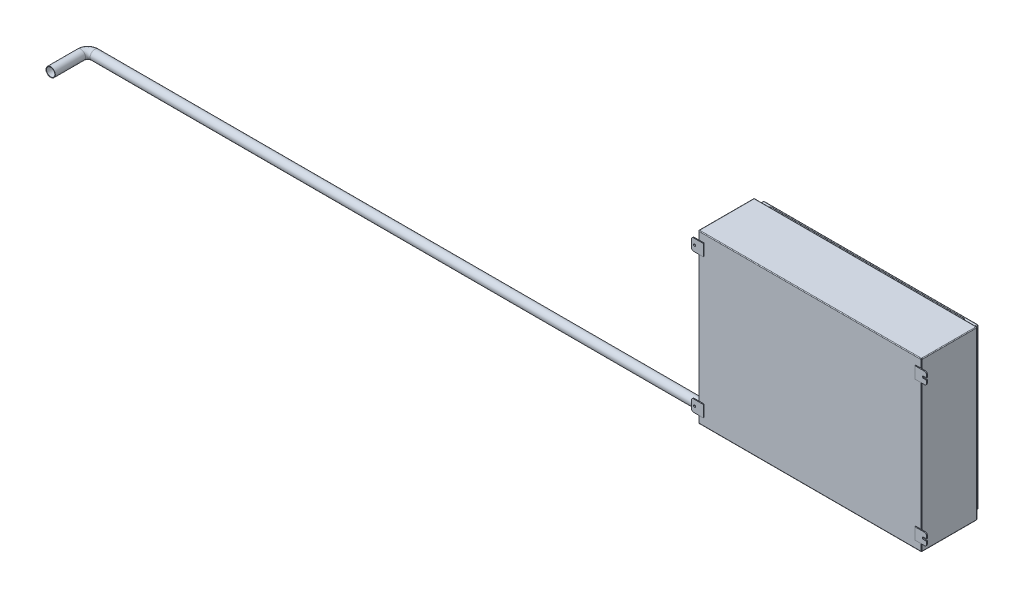
SolidWorks part; units mm, degrees
ref_plane "Front Plane" through (0, 0, 0) normal (0, 0, 1) x (1, 0, 0)
ref_plane "Top Plane" through (0, 0, 0) normal (0, 1, 0) x (1, 0, 0)
ref_plane "Right Plane" through (0, 0, 0) normal (1, 0, 0) x (0, 0, -1)
sketch "Sketch1" plane through (0, 0, 0) normal (0, 0, 1) x (1, 0, 0)
  line L0 (-609.6, -457.2) -> (609.6, 457.2) construction
  line L1 (-609.6, 457.2) -> (609.6, 457.2)
  line L2 (-609.6, 457.2) -> (-609.6, -457.2)
  line L3 (-609.6, -457.2) -> (609.6, -457.2)
  line L4 (609.6, 457.2) -> (609.6, -457.2)
  line L5 (-607.7026, 455.3026) -> (-607.7026, -455.3026)
  line L6 (-607.7026, -455.3026) -> (607.7026, -455.3026)
  line L7 (607.7026, 455.3026) -> (607.7026, -455.3026)
  line L8 (-607.7026, 455.3026) -> (607.7026, 455.3026)
  line L9 (571.5, -419.1) -> (-571.5, 419.1) construction
  line L10 (-571.5, 419.1) -> (571.5, 419.1)
  line L11 (-571.5, 419.1) -> (-571.5, -419.1)
  line L12 (-571.5, -419.1) -> (571.5, -419.1)
  line L13 (571.5, 419.1) -> (571.5, -419.1)
  line L14 (-549.275, 396.875) -> (-549.275, -396.875) construction
  line L15 (-549.275, -396.875) -> (549.275, -396.875) construction
  line L16 (549.275, 396.875) -> (549.275, -396.875) construction
  line L17 (-549.275, 396.875) -> (549.275, 396.875) construction
  line L18 (609.6, 412.75) -> (641.35, 412.75)
  line L19 (641.35, 412.75) -> (641.35, 386.5562)
  line L21 (-641.35, 349.25) -> (-609.6, 349.25)
  line L22 (0, 0) -> (0, 396.875) construction
  line L23 (-609.6, 412.75) -> (-641.35, 412.75)
  line L25 (-641.35, 412.75) -> (-641.35, 349.25)
  line L26 (0, 0) -> (0, 125.3343) construction
  line L27 (-544.5125, 396.875) -> (-544.5125, -396.875) construction
  line L28 (625.475, 375.4437) -> (609.6, 375.4437) construction
  line L29 (-625.475, 381) -> (-625.475, 349.25) construction
  line L30 (641.35, 349.25) -> (609.6, 349.25)
  line L31 (625.475, 375.4437) -> (641.35, 375.4437)
  line L32 (625.475, 386.5562) -> (641.35, 386.5562)
  line L33 (641.35, 375.4437) -> (641.35, 349.25)
  line L34 (625.475, 381) -> (625.475, 412.75) construction
  line L35 (-625.475, 365.125) -> (-609.6, 365.125) construction
  line L36 (0, 0) -> (571.5, 0) construction
  line L37 (-625.475, 381) -> (625.475, 381) construction
  line L38 (-641.35, -349.25) -> (-609.6, -349.25)
  line L39 (-641.35, -412.75) -> (-641.35, -349.25)
  line L40 (-609.6, -412.75) -> (-641.35, -412.75)
  line L41 (641.35, -349.25) -> (609.6, -349.25)
  line L42 (641.35, -375.4437) -> (641.35, -349.25)
  line L43 (625.475, -375.4437) -> (641.35, -375.4437)
  line L44 (641.35, -412.75) -> (641.35, -386.5562)
  line L45 (625.475, -386.5562) -> (641.35, -386.5562)
  line L46 (609.6, -412.75) -> (641.35, -412.75)
  circle A0 centre (549.275, 396.875) radius 4.7625 construction
  circle A1 centre (549.275, -396.875) radius 4.7625 construction
  circle A2 centre (-549.275, -396.875) radius 4.7625 construction
  circle A3 centre (-549.275, 396.875) radius 4.7625 construction
  circle A4 centre (-625.475, 381) radius 5.5563
  arc A6 (625.475, 386.5562) -> (625.475, 375.4437) centre (625.475, 381) ccw
  circle A12 centre (-625.475, -381) radius 5.5563
  arc A13 (625.475, -386.5562) -> (625.475, -375.4437) centre (625.475, -381) cw
  circle A14 centre (0, 396.875) radius 4.7625 construction
  circle A15 centre (0, -396.875) radius 4.7625 construction
  dimension "panel screw hole" = 9.525
  dimension "D6" = 11.1125
  dimension "D1" = 63.5
  dimension "D3" = 1250.95
  dimension "D2" = 22.225
sketch "Sketch2" plane through (0, 0, 0) normal (0, 1, 0) x (1, 0, 0)
  line L0 (-609.6, -152.4) -> (609.6, 152.4) construction
  line L1 (-609.6, 152.4) -> (609.6, 152.4)
  line L2 (-609.6, 152.4) -> (-609.6, -152.4)
  line L3 (-609.6, -152.4) -> (609.6, -152.4)
  line L4 (609.6, 152.4) -> (609.6, -152.4)
  line L5 (-607.7026, 150.5026) -> (-607.7026, -150.5026)
  line L6 (-571.5, -122.8166) -> (571.5, -122.8166)
  line L7 (-571.5, -122.8166) -> (-571.5, -125.4735)
  line L8 (-571.5, -125.4735) -> (571.5, -125.4735)
  line L9 (571.5, -122.8166) -> (571.5, -125.4735)
  line L10 (-607.7026, -150.5026) -> (607.7026, -150.5026)
  line L11 (607.7026, 150.5026) -> (607.7026, -150.5026)
  line L12 (-607.7026, 150.5026) -> (607.7026, 150.5026)
  line L13 (-609.6, 152.4) -> (609.6, 152.4) construction
  line L14 (-574.675, 152.4) -> (-574.675, 150.5026) construction
  line L15 (574.675, 152.4) -> (574.675, 150.5026) construction
  line L16 (-586.613, 173.482) -> (586.613, 173.482) construction
  line L17 (0, 0) -> (0, 173.482) construction
  line L18 (-586.613, 179.9666) -> (586.613, 179.9666) construction
  line L19 (-577.85, -152.4) -> (577.85, -152.4) construction
  line L20 (-641.35, -152.4) -> (-577.85, -152.4)
  line L21 (-641.35, -152.4) -> (-641.35, -157.226)
  line L22 (-641.35, -157.226) -> (-577.85, -157.226)
  line L23 (-577.85, -152.4) -> (-577.85, -157.226)
  line L24 (577.85, -152.4) -> (641.35, -152.4)
  line L25 (577.85, -152.4) -> (577.85, -157.226)
  line L26 (577.85, -157.226) -> (641.35, -157.226)
  line L27 (641.35, -152.4) -> (641.35, -157.226)
  line L28 (0, 0) -> (0, -152.4) construction
  line L29 (-586.613, 181.864) -> (586.613, 181.864) construction
  line L30 (-577.0499, 152.4) -> (-577.0499, 150.5026) construction
  dimension "D4" = 34.925
  dimension "P" = 1173.226
  dimension "D6" = 4.826
  dimension "D2" = 27.686
  dimension "D7" = 1.8974
  dimension "D8" = 29.464
  dimension "D9" = 63.5
  dimension "D10" = 32.5501
  dimension "D3" = 34.925
  dimension "D5" = 21.082
  dimension "D1" = 1.8974
sketch "Sketch4" plane through (0, 0, 0) normal (0, 0, 1) x (1, 0, 0)
  line L1 (-609.6, -457.2) -> (609.6, -457.2) construction
  line L2 (609.6, 457.2) -> (609.6, -457.2) construction
  line L4 (-609.6, 457.2) -> (609.6, 457.2) construction
  line L7 (-609.6, 457.2) -> (-609.6, -457.2) construction
  line L9 (-609.6, -457.2) -> (609.6, -457.2)
  line L10 (609.6, 457.2) -> (609.6, -457.2)
  line L12 (-609.6, 457.2) -> (609.6, 457.2)
  line L15 (-609.6, 457.2) -> (-609.6, -457.2)
extrude "Extrude1" add sketch "Sketch4" along normal mid plane 304.8
sketch "Sketch27" plane through (0, 0, -152.4) normal (0, 0, -1) x (-1, 0, 0)
  line L0 (609.6, 457.2) -> (609.6, -457.2) construction
  line L1 (574.675, -422.275) -> (-574.675, -422.275) construction
  line L2 (574.675, -422.275) -> (574.675, 422.275) construction
  line L3 (574.675, 422.275) -> (-574.675, 422.275) construction
  line L4 (-574.675, -422.275) -> (-574.675, 422.275) construction
  line L5 (609.6, 457.2) -> (-609.6, 457.2) construction
  line L10 (609.6, -457.2) -> (-609.6, -457.2) construction
  line L11 (578.4698, -426.0698) -> (-578.4698, -426.0698)
  line L12 (-578.4698, -426.0698) -> (-578.4698, 426.0698)
  line L13 (578.4698, 426.0698) -> (-578.4698, 426.0698)
  line L14 (578.4698, -426.0698) -> (578.4698, 426.0698)
  dimension "D1" = 34.925
  dimension "D2" = 34.925
  dimension "D3" = 34.925
  dimension "D4" = 3.7948
extrude "Extrude19" add sketch "Sketch27" along normal up to vertex (21.082 mm away) up to point (586.613, 0, -173.482)
fillet "Fillet1" radius 3.7948 20 edges at (609.6, -457.2, 0) (0, -457.2, -152.4) (609.6, 0, -152.4) (609.6, 0, 152.4) (0, -457.2, 152.4) (609.6, 457.2, 0) (0, 457.2, 152.4) (0, 457.2, -152.4) (-609.6, 457.2, 0) (-609.6, 0, 152.4) (-609.6, -457.2, 0) (-609.6, 0, -152.4) (0, 426.0698, -152.4) (578.4698, 0, -152.4) (0, -426.0698, -152.4) (-578.4698, 0, -152.4) (578.4698, -426.0698, -162.941) (578.4698, 426.0698, -162.941) (-578.4698, 426.0698, -162.941) (-578.4698, -426.0698, -162.941)
shell "Shell1" thickness 1.8974
sketch "Sketch5" plane through (0, 0, -173.482) normal (0, 0, -1) x (-1, 0, 0)
  line L8 (-576.5724, 422.275) -> (-576.5724, -422.275)
  line L9 (574.675, 424.1724) -> (-574.675, 424.1724)
  line L10 (576.5724, -422.275) -> (576.5724, 422.275)
  line L11 (-574.675, -424.1724) -> (574.675, -424.1724)
  line L12 (-576.5724, 422.275) -> (-576.5724, -422.275)
  line L13 (574.675, 424.1724) -> (-574.675, 424.1724)
  line L14 (576.5724, -422.275) -> (576.5724, 422.275)
  line L15 (-574.675, -424.1724) -> (574.675, -424.1724)
  arc A4 (-574.675, 424.1724) -> (-576.5724, 422.275) centre (-574.675, 422.275) ccw
  arc A5 (576.5724, 422.275) -> (574.675, 424.1724) centre (574.675, 422.275) ccw
  arc A6 (574.675, -424.1724) -> (576.5724, -422.275) centre (574.675, -422.275) ccw
  arc A7 (-576.5724, -422.275) -> (-574.675, -424.1724) centre (-574.675, -422.275) ccw
  arc A8 (-574.675, 424.1724) -> (-576.5724, 422.275) centre (-574.675, 422.275) ccw
  arc A9 (576.5724, 422.275) -> (574.675, 424.1724) centre (574.675, 422.275) ccw
  arc A10 (574.675, -424.1724) -> (576.5724, -422.275) centre (574.675, -422.275) ccw
  arc A11 (-576.5724, -422.275) -> (-574.675, -424.1724) centre (-574.675, -422.275) ccw
  dimension "D1" = 0
extrude "Cut-Extrude1" cut sketch "Sketch5" against normal blind 1.8974
sketch "Sketch50" plane through (0, 0, -152.4) normal (0, 0, -1) x (-1, 0, 0)
  line L0 (-609.6, 0) -> (-582.2645, 0) construction
  line L1 (-582.2645, -422.275) -> (-582.2645, 422.275) construction
  line L2 (-609.6, -453.4052) -> (-609.6, 453.4052) construction
  dimension "D1" = 27.3355
sketch "Sketch6" plane through (0, 0, 152.4) normal (0, 0, 1) x (1, 0, 0)
  line L6 (-641.35, 349.25) -> (-609.6, 349.25) construction
  line L7 (-609.6, 412.75) -> (-641.35, 412.75) construction
  line L8 (-641.35, 412.75) -> (-641.35, 349.25) construction
  line L9 (-641.35, 349.25) -> (-609.6, 349.25)
  line L10 (-609.6, 412.75) -> (-641.35, 412.75)
  line L11 (-641.35, 412.75) -> (-641.35, 349.25)
  line L12 (641.35, 349.25) -> (609.6, 349.25) construction
  line L13 (641.35, 375.4437) -> (641.35, 349.25) construction
  line L14 (625.475, 375.4437) -> (641.35, 375.4437) construction
  line L15 (625.475, 386.5562) -> (641.35, 386.5562) construction
  line L16 (641.35, 412.75) -> (641.35, 386.5562) construction
  line L17 (609.6, 412.75) -> (641.35, 412.75) construction
  line L18 (641.35, 349.25) -> (609.6, 349.25)
  line L19 (641.35, 375.4437) -> (641.35, 349.25)
  line L20 (625.475, 375.4437) -> (641.35, 375.4437)
  line L21 (625.475, 386.5562) -> (641.35, 386.5562)
  line L22 (641.35, 412.75) -> (641.35, 386.5562)
  line L23 (609.6, 412.75) -> (641.35, 412.75)
  line L24 (-609.6, 412.75) -> (-577.85, 412.75)
  line L25 (-577.85, 412.75) -> (-577.85, 349.25)
  line L26 (-609.6, 349.25) -> (-577.85, 349.25)
  line L27 (609.6, 412.75) -> (577.85, 412.75)
  line L28 (577.85, 412.75) -> (577.85, 349.25)
  line L29 (609.6, 349.25) -> (577.85, 349.25)
  line L30 (0, 0) -> (609.6, 0) construction
  line L31 (609.6, 457.2) -> (609.6, -457.2) construction
  line L32 (609.6, -349.25) -> (577.85, -349.25)
  line L33 (577.85, -412.75) -> (577.85, -349.25)
  line L34 (609.6, -412.75) -> (577.85, -412.75)
  line L35 (-609.6, -349.25) -> (-577.85, -349.25)
  line L36 (-577.85, -412.75) -> (-577.85, -349.25)
  line L37 (-609.6, -412.75) -> (-577.85, -412.75)
  line L38 (609.6, -412.75) -> (641.35, -412.75)
  line L39 (641.35, -412.75) -> (641.35, -386.5562)
  line L40 (625.475, -386.5562) -> (641.35, -386.5562)
  line L41 (625.475, -375.4437) -> (641.35, -375.4437)
  line L42 (641.35, -375.4437) -> (641.35, -349.25)
  line L43 (641.35, -349.25) -> (609.6, -349.25)
  line L44 (-641.35, -412.75) -> (-641.35, -349.25)
  line L45 (-609.6, -412.75) -> (-641.35, -412.75)
  line L46 (-641.35, -349.25) -> (-609.6, -349.25)
  circle A7 centre (-625.475, 381) radius 5.5563 construction
  circle A8 centre (-625.475, 381) radius 5.5563
  arc A9 (625.475, 386.5562) -> (625.475, 375.4437) centre (625.475, 381) ccw construction
  arc A10 (625.475, 386.5562) -> (625.475, 375.4437) centre (625.475, 381) ccw
  arc A11 (625.475, -386.5562) -> (625.475, -375.4437) centre (625.475, -381) cw
  circle A12 centre (-625.475, -381) radius 5.5563
extrude "Extrude2" add sketch "Sketch6" along normal up to vertex (4.826 mm away) up to point (641.35, 0, 157.226)
sketch "Sketch16" plane through (0, 0, 150.5026) normal (0, 0, -1) x (-1, 0, 0)
  circle A0 centre (-549.275, 396.875) radius 8.3344
  circle A1 centre (549.275, 396.875) radius 8.3344
  circle A2 centre (549.275, -396.875) radius 8.3344
  circle A3 centre (-549.275, -396.875) radius 8.3344
  circle A4 centre (-549.275, 396.875) radius 4.7625 construction
  circle A5 centre (-549.275, -396.875) radius 4.7625 construction
  circle A6 centre (549.275, -396.875) radius 4.7625 construction
  circle A7 centre (0, 396.875) radius 8.3344
  circle A8 centre (-549.275, 396.875) radius 4.7625
  circle A9 centre (-549.275, -396.875) radius 4.7625
  circle A10 centre (549.275, -396.875) radius 4.7625
  circle A13 centre (549.275, 396.875) radius 4.7625
  circle A16 centre (0, 396.875) radius 4.7625 construction
  circle A17 centre (0, 396.875) radius 4.7625
  circle A18 centre (0, -396.875) radius 8.3344
  circle A19 centre (0, -396.875) radius 4.7625 construction
  circle A20 centre (0, -396.875) radius 4.7625
  dimension "D1" = 16.6688
  dimension "D2" = 9.525
extrude "Extrude6" add sketch "Sketch16" along normal up to vertex (25.0292 mm away) up to point (571.5, 0, 125.4735)
sketch "Sketch17" plane through (0, 0, 150.5026) normal (0, 0, -1) x (-1, 0, 0)
  circle A1 centre (-549.275, 396.875) radius 4.7625
  circle A2 centre (-549.275, 396.875) radius 4.7625
  circle A5 centre (0, -396.875) radius 4.7625 construction
  circle A6 centre (0, -396.875) radius 4.7625
  circle A11 centre (549.275, 396.875) radius 4.7625
  circle A12 centre (549.275, 396.875) radius 4.7625
  circle A13 centre (549.275, -396.875) radius 4.7625
  circle A14 centre (549.275, -396.875) radius 4.7625
  circle A15 centre (-549.275, -396.875) radius 4.7625
  circle A16 centre (-549.275, -396.875) radius 4.7625
  circle A20 centre (0, 396.875) radius 4.7625 construction
  circle A21 centre (0, 396.875) radius 4.7625
  dimension "D1" = 0
  dimension "D6" = 0
  dimension "D7" = 0
  dimension "D8" = 0
extrude "Extrude7" add sketch "Sketch17" along normal offset from surface (40.9042 mm away) 15.875 up to face at (540.9406, 396.875, 125.4735) offset beyond the face yes
sketch "Sketch18" plane through (0, 0, 125.4735) normal (0, 0, -1) x (-1, 0, 0)
  line L0 (571.5, -419.1) -> (-571.5, -419.1) construction
  line L1 (571.5, 419.1) -> (571.5, -419.1) construction
  line L2 (571.5, 419.1) -> (-571.5, 419.1) construction
  line L3 (-571.5, 419.1) -> (-571.5, -419.1) construction
  line L4 (571.5, -419.1) -> (-571.5, -419.1)
  line L5 (571.5, 419.1) -> (571.5, -419.1)
  line L6 (571.5, 419.1) -> (-571.5, 419.1)
  line L7 (-571.5, 419.1) -> (-571.5, -419.1)
  circle A1 centre (549.275, 396.875) radius 5.5245
  circle A2 centre (549.275, -396.875) radius 5.5245
  circle A3 centre (549.275, -396.875) radius 5.5245
  circle A4 centre (-549.275, 396.875) radius 5.5245
  circle A5 centre (-549.275, -396.875) radius 5.5245
  dimension "D1" = 0.762
extrude "Extrude8" add sketch "Sketch18" along normal up to vertex (2.6568 mm away) up to point (571.5, 0, 122.8166)
ref_plane "Plane1" through (0, 0, -181.864) normal (0, 0, 1) x (1, 0, 0)
sketch "Sketch7" plane through (0, 0, -181.864) normal (0, 0, 1) x (1, 0, 0)
  line L0 (-609.6, 457.2) -> (609.6, 457.2) construction
  line L1 (-586.613, 441.198) -> (586.613, 441.198)
  line L2 (-586.613, 441.198) -> (-586.613, -431.8)
  line L3 (-586.613, -431.8) -> (586.613, -431.8)
  line L4 (586.613, 441.198) -> (586.613, -431.8)
  line L5 (-609.6, -457.2) -> (609.6, -457.2) construction
  line L6 (0, 0) -> (0, -431.8) construction
  line L7 (-609.6, -457.2) -> (609.6, 457.2) construction
  dimension "D1" = 872.998
  dimension "D2" = 25.4
  dimension "D3" = 16.002
  dimension "D4" = 1173.226
extrude "Extrude3" add sketch "Sketch7" along normal blind 17.4625 separate body
fillet "Fillet2" radius 3.7948 8 edges at (0, -431.8, -181.864) (586.613, 4.699, -181.864) (0, 441.198, -181.864) (-586.613, 4.699, -181.864) (-586.613, -431.8, -173.1327) (-586.613, 441.198, -173.1327) (586.613, -431.8, -173.1327) (586.613, 441.198, -173.1327)
shell "Shell2" thickness 1.8974 removed face at (0, 4.699, -164.4015)
ref_plane "Plane2" through (0, 437.4032, 0) normal (0, 1, 0) x (-1, 0, 0)
sketch "Sketch8" plane through (0, 437.4032, 0) normal (0, 1, 0) x (-1, 0, 0)
  line L0 (-586.613, -164.4015) -> (-584.7156, -164.4015)
  line L1 (-584.7156, -164.4015) -> (-584.7156, -163.3753)
  line L2 (-588.0177, -160.9663) -> (-593.0976, -162.5947)
  line L3 (-593.0976, -162.5947) -> (-592.5184, -164.4015)
  line L4 (-592.5184, -164.4015) -> (-587.4385, -162.7731)
  line L5 (-586.613, -164.4015) -> (-586.613, -163.3753)
  line L7 (-586.613, -164.4015) -> (-586.613, -178.0692) construction
  line L8 (582.8182, -164.4015) -> (-582.8182, -164.4015) construction
  line L10 (-190.1607, -160.8455) -> (-179.6224, -160.8455) construction
  arc A0 (-584.7156, -163.3753) -> (-588.0177, -160.9663) centre (-587.2455, -163.3753) ccw
  arc A1 (-587.4385, -162.7731) -> (-586.613, -163.3753) centre (-587.2455, -163.3753) cw
  dimension "D5" = 0.6325
  dimension "D4" = 1.8974
  dimension "D2" = 8.382
  dimension "D3" = 3.556
sketch "Sketch9" plane through (0, 0, -164.4015) normal (0, 0, 1) x (1, 0, 0)
  line L0 (586.613, -428.0052) -> (586.613, 437.4032) construction
  line L1 (-582.8182, -431.8) -> (582.8182, -431.8) construction
  line L2 (586.613, -428.0052) -> (586.613, 437.4032)
  line L3 (-582.8182, -431.8) -> (582.8182, -431.8)
  line L4 (-586.613, 437.4032) -> (-586.613, -428.0052) construction
  line L5 (-586.613, 437.4032) -> (-586.613, -428.0052)
  arc A0 (582.8182, -431.8) -> (586.613, -428.0052) centre (582.8182, -428.0052) ccw construction
  arc A1 (582.8182, -431.8) -> (586.613, -428.0052) centre (582.8182, -428.0052) ccw
  arc A2 (-586.613, -428.0052) -> (-582.8182, -431.8) centre (-582.8182, -428.0052) ccw construction
  arc A3 (-586.613, -428.0052) -> (-582.8182, -431.8) centre (-582.8182, -428.0052) ccw
sweep "Sweep1" add profiles "Sketch8" path "Sketch9"
sketch "Sketch10" plane through (0, 0, -164.4015) normal (0, 0, 1) x (1, 0, 0)
  line L1 (-654.9517, 519.8491) -> (654.9517, 519.8491)
  line L2 (-654.9517, 519.8491) -> (-654.9517, 392.8491)
  line L3 (-654.9517, 392.8491) -> (654.9517, 392.8491)
  line L4 (654.9517, 519.8491) -> (654.9517, 392.8491)
  line L5 (-654.9517, -392.8491) -> (-527.9517, -392.8491)
  line L6 (-654.9517, -392.8491) -> (-654.9517, -519.8491)
  line L7 (-654.9517, -519.8491) -> (-527.9517, -519.8491)
  line L8 (-527.9517, -392.8491) -> (-527.9517, -519.8491)
  line L9 (527.9517, -392.8491) -> (654.9517, -392.8491)
  line L10 (527.9517, -392.8491) -> (527.9517, -519.8491)
  line L11 (527.9517, -519.8491) -> (654.9517, -519.8491)
  line L12 (654.9517, -392.8491) -> (654.9517, -519.8491)
  line L14 (-591.4517, -392.8491) -> (-591.4517, 392.8491) construction
  line L17 (-591.4517, 0) -> (0, 0) construction
  line L18 (-527.9517, -456.3491) -> (527.9517, -456.3491) construction
  line L19 (0, -456.3491) -> (0, 0) construction
  dimension "D5" = 127
  dimension "D1" = 785.6982
  dimension "D2" = 1055.9034
extrude "Cut-Extrude2" cut sketch "Sketch10" along normal blind 12.7 draft 30 draft outward yes
sketch "Sketch11" plane through (0, 0, -181.864) normal (0, 0, -1) x (-1, 0, 0)
  line L0 (527.0115, -432.6255) -> (528.0589, -438.2846)
  line L1 (528.0589, -438.2846) -> (523.7442, -438.2846)
  line L2 (527.0115, -432.6255) -> (523.7442, -438.2846)
  line L3 (527.0115, -432.6255) -> (527.9517, -437.7054) construction
  line L4 (-526.9085, -438.2846) -> (526.9085, -438.2846) construction
  line L5 (587.4385, -391.9089) -> (593.0976, -392.9563)
  line L6 (593.0976, -392.9563) -> (593.0976, -388.6416)
  line L7 (593.0976, -388.6416) -> (587.4385, -391.9089)
  line L8 (592.5184, -392.8491) -> (587.4385, -391.9089) construction
  line L9 (593.0976, -391.8059) -> (593.0976, 391.8059) construction
  line L10 (592.5184, 0) -> (16.547, 0) construction
  line L11 (592.5184, -392.8491) -> (592.5184, 392.8491) construction
  line L12 (593.0976, 388.6416) -> (587.4385, 391.9089)
  line L13 (593.0976, 392.9563) -> (593.0976, 388.6416)
  line L14 (587.4385, 391.9089) -> (593.0976, 392.9563)
  line L15 (0, -437.7054) -> (0, -6.7093) construction
  line L16 (-527.9517, -437.7054) -> (527.9517, -437.7054) construction
  line L17 (-587.4385, 391.9089) -> (-593.0976, 392.9563)
  line L18 (-593.0976, 392.9563) -> (-593.0976, 388.6416)
  line L19 (-593.0976, 388.6416) -> (-587.4385, 391.9089)
  line L20 (-593.0976, -388.6416) -> (-587.4385, -391.9089)
  line L21 (-593.0976, -392.9563) -> (-593.0976, -388.6416)
  line L22 (-587.4385, -391.9089) -> (-593.0976, -392.9563)
  line L23 (-527.0115, -432.6255) -> (-523.7442, -438.2846)
  line L24 (-528.0589, -438.2846) -> (-523.7442, -438.2846)
  line L25 (-527.0115, -432.6255) -> (-528.0589, -438.2846)
  ellipse E0 centre (527.3592, -432.4325) end of major axis (527.3592, -433.0649) minor radius 0.3652 (527.3592, -431.8) -> (527.0115, -432.6255) ccw construction
  ellipse E1 centre (587.2455, -392.2566) end of major axis (587.8779, -392.2566) minor radius 0.3652 (587.4385, -391.9089) -> (586.613, -392.2566) ccw construction
  dimension "D1" = 60
  dimension "D2" = 60
extrude "Cut-Extrude3" cut sketch "Sketch11" against normal through all
sketch "Sketch12" plane through (0, 0, 0) normal (1, 0, 0) x (0, 0, -1)
  line L1 (163.4528, 447.8788) -> (163.4528, 439.3006) construction
  line L2 (163.4528, 439.3006) -> (178.0692, 439.3006) construction
  line L3 (178.0692, 439.3006) -> (178.0692, 437.4032) construction
  line L4 (178.0692, 437.4032) -> (161.5554, 437.4032) construction
  line L5 (161.5554, 437.4032) -> (161.5554, 443.7109) construction
  line L7 (178.0692, 439.3006) -> (164.4015, 439.3006) construction
  line L8 (152.4, 447.8788) -> (152.4, 429.8645)
  line L9 (152.4, 429.8645) -> (154.2974, 429.8645)
  line L10 (154.2974, 429.8645) -> (154.2974, 443.7109)
  line L11 (154.2974, 443.7109) -> (157.9264, 447.8788) construction
  line L12 (154.2974, 443.7109) -> (154.2974, 447.8788)
  line L13 (155.9499, 444.8353) -> (154.6959, 443.395)
  line L16 (178.0692, 437.4032) -> (178.0692, -428.0052) construction
  line L17 (148.6052, 453.4052) -> (-148.6052, 453.4052) construction
  line L18 (164.4015, 441.198) -> (164.4015, 437.4032) construction
  line L19 (152.4, 453.4052) -> (152.4, -453.4052) construction
  arc A4 (155.9499, 444.8353) -> (154.2974, 447.8788) centre (157.9264, 447.8788) ccw
  arc A5 (154.6959, 443.395) -> (152.4, 447.8788) centre (157.9264, 447.8788) ccw
  dimension "D1" = 1.8974
  dimension "D4" = 1.8974
  dimension "D3" = 0.508
  dimension "D2" = 0.9487
extrude "Extrude4" add sketch "Sketch12" along normal mid plane 1055.9034 separate body
sketch "Sketch13" plane through (0, 0, 0) normal (1, 0, 0) x (0, 0, -1)
  line L0 (179.9666, 439.3006) -> (163.4528, 439.3006)
  line L1 (163.4528, 447.8788) -> (163.4528, 439.3006) construction
  line L2 (161.5554, 437.4032) -> (161.5554, 443.7109) construction
  line L3 (179.9666, 439.3006) -> (179.9666, 437.4032)
  line L4 (179.9666, 437.4032) -> (161.5554, 437.4032)
  line L5 (163.4528, 447.8788) -> (163.4528, 439.3006)
  line L6 (161.5554, 437.4032) -> (161.5554, 443.7109)
  line L10 (178.0692, 439.3006) -> (164.4015, 439.3006) construction
  line L13 (179.9666, -428.0052) -> (179.9666, 437.4032) construction
  line L14 (152.4, 429.8645) -> (154.2974, 429.8645) construction
  arc A0 (163.4528, 447.8788) -> (161.5554, 443.7109) centre (157.9264, 447.8788) ccw
  arc A1 (154.6959, 443.395) -> (152.4, 447.8788) centre (157.9264, 447.8788) ccw construction
  circle A2 centre (157.9264, 447.8788) radius 3.629
  arc A4 (155.9499, 444.8353) -> (154.2974, 447.8788) centre (157.9264, 447.8788) ccw construction
extrude "Extrude5" add sketch "Sketch13" along normal mid plane 1055.9034 separate body
sketch "Sketch14" plane through (0, 306.3189, -152.4) normal (0, 0, 1) x (1, 0, 0)
  line L1 (-21.1181, 147.0863) -> (21.1181, 147.0863)
  line L2 (-21.1181, 147.0863) -> (-21.1181, 134.7635)
  line L3 (-21.1181, 134.7635) -> (21.1181, 134.7635)
  line L4 (21.1181, 147.0863) -> (21.1181, 134.7635)
  line L5 (527.9517, 147.0863) -> (-527.9517, 147.0863) construction
  line L7 (527.9517, 123.5456) -> (-527.9517, 123.5456) construction
  line L8 (0, -306.3189) -> (0, 134.7635) construction
  line L9 (-527.9517, 136.0335) -> (527.9517, 136.0335) construction
  dimension "D1" = 1055.9034
  dimension "D2" = 42.2361
  dimension "D3" = 1.27
extrude "Cut-Extrude4" cut sketch "Sketch14" against normal mid plane 25.4
pattern_linear "LPattern1" count 8 spacing 84.4723 along (-1, 0, 0) count 8 spacing 84.4723 along (1, 0, 0) of "Cut-Extrude4"
sketch "Sketch15" plane through (0, 216.0613, -161.5554) normal (0, 0, 1) x (1, 0, 0)
  line L0 (-21.1181, 225.0211) -> (21.1181, 225.0211) construction
  line L1 (-63.3542, 225.9101) -> (-21.1181, 225.9101)
  line L2 (-63.3542, 225.9101) -> (-63.3542, 237.3439)
  line L3 (-63.3542, 237.3439) -> (-21.1181, 237.3439)
  line L4 (-21.1181, 225.9101) -> (-21.1181, 237.3439)
  line L7 (527.9517, 237.3439) -> (-527.9517, 237.3439) construction
  line L8 (-527.9517, 226.2911) -> (527.9517, 226.2911) construction
  dimension "D1" = 0.381
extrude "Cut-Extrude5" cut sketch "Sketch15" along normal through all and the other way through all
pattern_linear "LPattern2" count 8 spacing 84.4723 along (-1, 0, 0) count 8 spacing 84.4723 along (1, 0, 0) of "Cut-Extrude5"
combine bodies "Combine1" operation type add bodies to combine 113 107
combine bodies "Combine2" operation type add bodies to combine 118 111
sketch "Sketch28" plane through (527.9517, 0, 0) normal (1, 0, 0) x (0, 0, -1)
  circle A0 centre (157.9264, 447.8788) radius 3.629
  circle A1 centre (157.9264, 447.8788) radius 3.629 construction
extrude "Extrude20" add sketch "Sketch28" against normal up to surface (1055.9034 mm away) separate body up to face at (-527.9517, 447.8788, -161.5554)
ref_plane "Plane3" through (571.5, 0, 0) normal (1, 0, 0) x (0, 0, -1)
ref_plane "Plane5" through (-0.254, 0, 0) normal (1, 0, 0) x (0, 0, -1)
sketch "Sketch29" plane through (-0.254, 0, 0) normal (1, 0, 0) x (0, 0, -1)
  line L0 (178.0692, -431.8) -> (164.2745, -431.8)
  line L1 (164.2745, -431.8) -> (164.2745, -453.4052)
  line L2 (178.0692, -431.8) -> (178.0692, -433.6974)
  line L3 (178.0692, -433.6974) -> (166.1719, -433.6974)
  line L4 (166.1719, -433.6974) -> (166.1719, -453.4052)
  line L5 (164.2745, -453.4052) -> (166.1719, -453.4052)
  line L6 (178.0692, -431.8) -> (164.4015, -431.8) construction
  line L7 (152.4, -453.4052) -> (148.6052, -453.4052) construction
  dimension "D1" = 1.8974
  dimension "D2" = 0.127
extrude "Extrude21" add sketch "Sketch29" along normal mid plane 53.975 separate body
fillet "Fillet6" radius 6.35 4 edges at (26.7335, -432.7487, -178.0692) (-27.2415, -432.7487, -178.0692) (-27.2415, -453.4052, -165.2232) (26.7335, -453.4052, -165.2232)
fillet "Fillet7" radius 2.032 1 edges at (-0.254, -431.8, -164.2745)
fillet "Fillet8" radius 0.254 1 edges at (-0.254, -433.6974, -166.1719)
sketch "Sketch30" plane through (0, 0, -166.1719) normal (0, 0, -1) x (-1, 0, 0)
  line L0 (0.254, -453.4052) -> (0.254, -450.2302) construction
  line L1 (12.554, -443.0801) -> (-12.0459, -443.0801)
  line L2 (-20.3835, -453.4052) -> (20.8915, -453.4052) construction
  line L3 (12.554, -450.2302) -> (-12.0459, -450.2302)
  arc A0 (12.554, -443.0801) -> (12.554, -450.2302) centre (12.554, -446.6552) cw
  arc A1 (-12.0459, -443.0801) -> (-12.0459, -450.2302) centre (-12.0459, -446.6552) ccw
  dimension "D1" = 31.75
  dimension "D2" = 7.1501
  dimension "D3" = 3.175
extrude "Cut-Extrude6" cut sketch "Sketch30" against normal up to vertex (1.8974 mm away) up to point (26.7335, -433.832, -164.2745)
ref_plane "Plane6" through (0, -446.6552, 0) normal (0, 1, 0) x (-1, 0, 0)
sketch "Sketch31" plane through (0, -446.6552, 0) normal (0, 1, 0) x (-1, 0, 0)
  line L0 (0.254, -164.2745) -> (0.254, -175.0619) construction
  line L1 (-6.096, -184.5869) -> (6.604, -184.5869)
  line L2 (-12.446, -178.2369) -> (-12.446, -152.4)
  line L3 (-12.446, -152.4) -> (12.954, -152.4)
  line L4 (12.954, -178.2369) -> (12.954, -152.4)
  line L5 (-605.8052, -152.4) -> (605.8052, -152.4) construction
  line L6 (-20.3835, -164.2745) -> (20.8915, -164.2745) construction
  line L8 (0.254, -181.4119) -> (0.254, -184.5869) construction
  circle A0 centre (0.254, -175.0619) radius 6.35
  arc A1 (6.604, -184.5869) -> (12.954, -178.2369) centre (6.604, -178.2369) ccw
  arc A2 (-6.096, -184.5869) -> (-12.446, -178.2369) centre (-6.096, -178.2369) cw
  point P15 (12.954, -184.5869)
  point P19 (-12.446, -184.5869)
  dimension "D3" = 12.7
  dimension "D4" = 2.54
  dimension "D5" = 6.35
  dimension "D1" = 25.4
  dimension "D2" = 3.175
extrude "Extrude22" add sketch "Sketch31" along normal mid plane 2.032 separate body
sketch "Sketch32" plane through (0, -447.6712, 0) normal (0, -1, 0) x (1, 0, 0)
  line L0 (-12.954, -178.2369) -> (-12.954, -152.4) construction
  line L1 (12.446, -152.4) -> (-12.954, -152.4)
  line L2 (12.446, -152.4) -> (12.446, -154.432)
  line L3 (12.446, -154.432) -> (-12.954, -154.432)
  line L4 (-12.954, -152.4) -> (-12.954, -154.432)
  dimension "D1" = 2.032
extrude "Extrude23" add sketch "Sketch32" against normal blind 15.875
fillet "Fillet11" radius 9.525 8 edges at (641.35, -349.25, 154.813) (641.35, 349.25, 154.813) (641.35, 412.75, 154.813) (641.35, -412.75, 154.813) (-641.35, -412.75, 154.813) (-641.35, -349.25, 154.813) (-641.35, 412.75, 154.813) (-641.35, 349.25, 154.813)
combine bodies "Combine6" operation type add bodies to combine 162 114
sketch "Sketch33" plane through (0, 0, -152.4) normal (0, 0, -1) x (-1, 0, 0)
  line L1 (13.6677, 28.575) -> (-13.6677, 28.575)
  line L2 (13.6677, 28.575) -> (13.6677, 15.875)
  line L3 (13.6677, -28.575) -> (-13.6677, -28.575)
  line L4 (-13.6677, 28.575) -> (-13.6677, -28.575)
  line L6 (13.6677, 15.875) -> (-0.9677, 15.875)
  line L7 (-0.9677, 15.875) -> (-0.9677, -15.875)
  line L8 (-0.9677, -15.875) -> (13.6677, -15.875)
  line L9 (13.6677, -15.875) -> (13.6677, -28.575)
  line L10 (-13.6677, 0) -> (-0.9677, 0) construction
  line L11 (0, -28.575) -> (0, 0) construction
  dimension "D1" = 57.15
  dimension "D2" = 12.7
  dimension "D3" = 27.3355
extrude "Extrude24" [suppressed] add sketch "Sketch33" along normal blind 2.032 separate body
sketch "Sketch34" [suppressed] plane through (0, 0, -154.432) normal (0, 0, -1) x (-1, 0, 0)
  line L1 (-13.6677, 10.4775) -> (-0.9677, 10.4775)
  line L2 (-13.6677, 10.4775) -> (-13.6677, -10.4775)
  line L3 (-13.6677, -10.4775) -> (-0.9677, -10.4775)
  line L4 (-0.9677, 10.4775) -> (-0.9677, -10.4775)
  line L5 (-0.9677, -15.875) -> (-0.9677, 15.875) construction
  line L6 (-13.6677, 0) -> (-0.9677, 0) construction
  line L7 (-13.6677, 28.575) -> (-13.6677, -28.575) construction
  dimension "D1" = 20.955
extrude "Extrude25" [suppressed] add sketch "Sketch34" along normal blind 12.065
sketch "Sketch35" [suppressed] plane through (13.6677, 0, 0) normal (1, 0, 0) x (0, 0, -1)
  line L0 (166.497, 10.4775) -> (154.432, 10.4775) construction
  line L1 (152.4, 7.3025) -> (163.322, 7.3025)
  line L2 (152.4, 7.3025) -> (152.4, -7.3025)
  line L3 (152.4, -7.3025) -> (163.322, -7.3025)
  line L4 (163.322, 7.3025) -> (163.322, -7.3025)
  line L5 (166.497, 10.4775) -> (166.497, -10.4775) construction
  line L6 (166.497, -10.4775) -> (154.432, -10.4775) construction
  line L7 (152.4, 28.575) -> (152.4, -28.575) construction
  dimension "D1" = 3.175
  dimension "D2" = 3.175
  dimension "D3" = 3.175
extrude "Cut-Extrude7" [suppressed] cut sketch "Sketch35" against normal through all
fillet "Fillet9" [suppressed] radius 2.032
fillet "Fillet10" [suppressed] radius 4.064
sketch "Sketch36" [suppressed] plane through (0, 0, -166.497) normal (0, 0, -1) x (-1, 0, 0)
  line L0 (-13.6677, -6.4135) -> (-0.9677, 6.4135) construction
  circle A0 centre (-7.3177, 0) radius 3.175
  dimension "D1" = 6.35
extrude "Cut-Extrude8" [suppressed] cut sketch "Sketch36" against normal through all
ref_plane "Plane7" [suppressed] through (0, 0, 0) normal (0, 1, 0) x (-1, 0, 0)
sketch "Sketch37" [suppressed] plane through (0, 0, 0) normal (0, 1, 0) x (-1, 0, 0)
  line L0 (6.176, -162.5041) -> (6.176, -173.6166)
  line L1 (1.4135, -178.3791) -> (-16.049, -178.3791)
  line L2 (-20.8115, -173.6166) -> (-20.8115, -160.2816)
  line L3 (-16.049, -155.5191) -> (-7.3177, -155.5191)
  line L4 (-7.3177, -166.497) -> (-7.3177, -178.3791) construction
  line L5 (-10.4927, -166.497) -> (-4.1427, -166.497) construction
  arc A0 (6.176, -173.6166) -> (1.4135, -178.3791) centre (1.4135, -173.6166) cw
  arc A1 (-16.049, -178.3791) -> (-20.8115, -173.6166) centre (-16.049, -173.6166) cw
  arc A2 (-20.8115, -160.2816) -> (-16.049, -155.5191) centre (-16.049, -160.2816) cw
  point P11 (6.176, -178.3791)
  point P14 (-20.8115, -178.3791)
  dimension "D3" = 4.7625
  dimension "D4" = 15.875
  dimension "D1" = 26.9875
  dimension "D2" = 22.86
  dimension "D5" = 11.8821
extrude "Extrude-Thin1" [suppressed] add sketch "Sketch37" along normal mid plane 31.75 separate body thin thin type one direction wall 2.54
sketch "Sketch38" [suppressed] plane through (0, 0, -155.5191) normal (0, 0, 1) x (1, 0, 0)
  line L0 (13.6677, 5.2705) -> (0.9677, 5.2705) construction
  line L1 (7.3177, 15.875) -> (20.8115, 15.875)
  line L2 (7.3177, 15.875) -> (7.3177, 5.2705)
  line L3 (7.3177, 5.2705) -> (20.8115, 5.2705)
  line L4 (20.8115, 15.875) -> (20.8115, 5.2705)
  line L5 (7.3177, -5.2705) -> (20.8115, -5.2705)
  line L6 (7.3177, -5.2705) -> (7.3177, -15.875)
  line L7 (7.3177, -15.875) -> (20.8115, -15.875)
  line L8 (20.8115, -5.2705) -> (20.8115, -15.875)
  line L9 (0.9677, -5.2705) -> (13.6677, -5.2705) construction
  line L10 (7.3177, 15.875) -> (7.3177, -15.875) construction
extrude "Cut-Extrude9" [suppressed] cut sketch "Sketch38" against normal up to vertex up to point (0, 20.8115, -15.875)
sketch "Sketch39" [suppressed] plane through (0, 0, -175.8391) normal (0, 0, 1) x (1, 0, 0)
  line L0 (1.7615, 3.175) -> (12.874, 3.175)
  line L1 (1.7615, -3.175) -> (12.874, -3.175)
  line L2 (-1.4135, 15.875) -> (-1.4135, -15.875) construction
  line L3 (16.049, 15.875) -> (16.049, -15.875) construction
  arc A0 (1.7615, 3.175) -> (1.7615, -3.175) centre (1.7615, 0) ccw
  arc A1 (12.874, -3.175) -> (12.874, 3.175) centre (12.874, 0) ccw
  circle A2 centre (7.3177, 0) radius 3.175 construction
extrude "Cut-Extrude10" [suppressed] cut sketch "Sketch39" against normal through all
sketch "Sketch40" [suppressed] plane through (0, 0, -158.0591) normal (0, 0, -1) x (-1, 0, 0)
  circle A3 centre (-7.3177, 0) radius 3.048
  circle A4 centre (-7.3177, 0) radius 3.048
  dimension "D1" = 0.127
extrude "Extrude27" [suppressed] add sketch "Sketch40" along normal up to surface (20.32 mm away)
sketch "Sketch41" [suppressed] plane through (0, 0, -178.3791) normal (0, 0, -1) x (-1, 0, 0)
  circle A0 centre (-7.3177, 0) radius 6.35
  circle A1 centre (-7.3177, 0) radius 3.048 construction
  dimension "D1" = 12.7
extrude "Extrude28" [suppressed] add sketch "Sketch41" along normal blind 1.143
sketch "Sketch42" [suppressed] plane through (0, 0, -179.5221) normal (0, 0, -1) x (-1, 0, 0)
  line L0 (-13.6677, -6.4135) -> (-0.9677, 6.4135) construction
  line L1 (-7.3177, 5.4993) -> (-12.0802, 2.7496)
  line L2 (-12.0802, 2.7496) -> (-12.0802, -2.7496)
  line L3 (-12.0802, -2.7496) -> (-7.3177, -5.4993)
  line L4 (-7.3177, -5.4993) -> (-2.5552, -2.7496)
  line L5 (-2.5552, -2.7496) -> (-2.5552, 2.7496)
  line L6 (-2.5552, 2.7496) -> (-7.3177, 5.4993)
  circle A0 centre (-7.3177, 0) radius 4.7625 construction
  dimension "D1" = 9.525
extrude "Extrude29" [suppressed] add sketch "Sketch42" along normal blind 4.7625
sketch "Sketch43" [suppressed] plane through (0, 0, -184.2846) normal (0, 0, -1) x (-1, 0, 0)
  circle A0 centre (-7.3177, 0) radius 4.7625 construction
  circle A1 centre (-7.3177, 0) radius 4.7625
extrude "Cut-Extrude11" [suppressed] cut sketch "Sketch43" against normal blind 2.54 draft 60 flip side to cut
sketch "Sketch44" [suppressed] plane through (0, 0, -184.2846) normal (0, 0, -1) x (-1, 0, 0)
  circle A2 centre (-7.3177, 0) radius 4.3815
  circle A3 centre (-7.3177, 0) radius 4.3815
  dimension "D1" = 0.381
extrude "Cut-Extrude12" [suppressed] cut sketch "Sketch44" against normal blind 0.762 draft 20
sketch "Sketch45" [suppressed] plane through (0, 0, -184.2846) normal (0, 0, -1) x (-1, 0, 0)
  line L0 (-11.8302, 4.4677) -> (-2.8053, -4.4677)
  line L1 (-13.6677, -6.4135) -> (-0.9677, 6.4135) construction
  circle A0 centre (-7.3177, 0) radius 6.35 construction
  arc A1 (-12.817, -3.175) -> (-1.8185, -3.175) centre (-7.3177, 0) ccw construction
  dimension "D1" = 90
extrude "Cut-Extrude-Thin1" [suppressed] cut sketch "Sketch45" against normal blind 1.778 thin thin type mid plane wall 1.778
sketch "Sketch46" [suppressed] plane through (0, 0, -166.497) normal (0, 0, -1) x (-1, 0, 0)
  line L4 (-13.6677, 6.4135) -> (-13.6677, -6.4135)
  line L5 (-13.6677, -6.4135) -> (-0.9677, -6.4135)
  line L6 (-0.9677, -6.4135) -> (-0.9677, 6.4135)
  line L7 (-0.9677, 6.4135) -> (-13.6677, 6.4135)
  line L8 (-13.6677, 6.4135) -> (-13.6677, -6.4135)
  line L9 (-13.6677, -6.4135) -> (-0.9677, -6.4135)
  line L10 (-0.9677, -6.4135) -> (-0.9677, 6.4135)
  line L11 (-0.9677, 6.4135) -> (-13.6677, 6.4135)
  dimension "D1" = 0
extrude "Extrude30" [suppressed] add sketch "Sketch46" against normal blind 0.508
sketch "Sketch47" [suppressed] plane through (0, 0, 0) normal (1, 0, 0) x (0, 0, -1)
  line L0 (0, 0) -> (178.3791, 0) construction
  line L1 (178.3791, 0) -> (178.3791, -15.875) construction
ref_axis "Axis1" through (0, 0, -173.482) along (0, 0, 1)
pattern_circular "CirPattern1" [suppressed] count 2 over 90 about axis through (0, 0, -173.482) along (0, 0, 1) of bodies 179
sketch "Sketch48" [suppressed] plane through (0, 0, -154.432) normal (0, 0, -1) x (-1, 0, 0)
  line L0 (-13.6677, -20.5422) -> (-609.6, -20.5423) construction
  line L1 (-13.6677, -12.5095) -> (-13.6677, -28.575) construction
  line L2 (-609.6, -453.4052) -> (-609.6, 453.4052) construction
  line L3 (-609.6, -20.5423) -> (-609.6, -371.348) construction
  line L4 (605.8052, -457.2) -> (-605.8052, -457.2) construction
  dimension "D1" = 595.9323
  dimension "D2" = 85.852
  dimension "D3" = 350.8058
sketch "Sketch49" [suppressed] plane through (0, 0, -154.432) normal (0, 0, -1) x (-1, 0, 0)
  line L0 (0, -13.6677) -> (0, -457.2) construction
  line L1 (0, -457.2) -> (-523.748, -457.2) construction
  line L2 (605.8052, -457.2) -> (-605.8052, -457.2) construction
  line L3 (-609.6, -453.4052) -> (-609.6, 453.4052) construction
  line L4 (-28.575, -13.6677) -> (-12.5095, -13.6677) construction
  point P10 (-261.874, -457.2)
  dimension "D1" = 85.852
  dimension "D2" = 443.5323
  dimension "D3" = 523.748
  dimension "D4" = 261.874
pattern_linear "LPattern7" [suppressed] count 2 spacing 595.9323 of bodies 179
mirror "Mirror4" [suppressed] about plane through (0, 0, 0) normal (1, 0, 0) of bodies 195
pattern_linear "LPattern8" [suppressed] count 2 spacing 443.5323 count 2 spacing 261.874 of bodies 180
pattern_linear "LPattern3" [suppressed] count 2 spacing 595.9323 of bodies 179
delete or keep bodies "Body-Delete1" [suppressed] type delete bodies bodies 179
pattern_linear "LPattern4" [suppressed] count 2 spacing 443.5323 count 2 spacing 523.748 of bodies 180
delete or keep bodies "Body-Delete2" [suppressed] type delete bodies bodies 180
mirror "Mirror1" [suppressed] about plane through (0, 0, 0) normal (1, 0, 0) of bodies 182 181
pattern_linear "LPattern5" [suppressed] count 2 spacing 595.9323 along (1, 0, 0) count 2 spacing 350.8058 along (0, -1, 0) of bodies 179 180
pattern_linear "LPattern6" [suppressed] count 2 spacing 443.5323 along (0, -1, 0) count 2 spacing 523.748 along (1, 0, 0) of bodies 180
mirror "Mirror2" [suppressed] about plane through (0, 0, 0) normal (0, 1, 0) of bodies 188
mirror "Mirror3" [suppressed] about plane through (0, 0, 0) normal (1, 0, 0) of bodies 190 188 194 189
delete or keep bodies "Body-Delete3" [suppressed] type delete bodies bodies 180 179
mirror "Mirror5" [suppressed] about plane through (0, 0, 0) normal (1, 0, 0) of bodies 197
delete or keep bodies "Body-Delete4" [suppressed] type delete bodies bodies 189
sketch "Sketch51" plane through (0, 0, -181.864) normal (0, 0, -1) x (-1, 0, 0)
  line L0 (71.5032, 413.5303) -> (71.5032, -428.0052) construction
  line L2 (-582.8182, -428.0052) -> (582.8182, -428.0052) construction
  text T0 "LIGHT DRIVERS \r\nENCLOSURE" font "Arial" height in points 300
  point P2 (75.7093, 428.9526)
  point P3 (71.5032, 413.5303)
  point P7 (0, 0)
extrude "Cut-Extrude13" cut sketch "Sketch51" against normal blind 0.508
sketch "Sketch52" plane through (-609.6, 0, 0) normal (-1, 0, 0) x (0, 0, 1)
  line L1 (-148.6052, -453.4052) -> (148.6052, -453.4052) construction
  line L2 (148.6052, -453.4052) -> (148.6052, 453.4052) construction
  line L3 (87.6452, -402.6052) -> (85.1052, -402.6052) construction
  circle A0 centre (110.5052, -402.6052) radius 25.4
  circle A1 centre (110.5052, -402.6052) radius 22.86
  dimension "D1" = 50.8
  dimension "D2" = 50.8
  dimension "D3" = 38.1
  dimension "D4" = 2.54
extrude "Boss-Extrude1" add sketch "Sketch52" along normal blind 3302 separate body
ref_axis "Axis2" through (-3911.6, -402.6052, 110.5052) along (1, 0, 0)
ref_plane "Plane8" through (0, -402.6052, 0) normal (0, 1, 0) x (1, 0, 0)
sketch "Sketch54" plane through (-3911.6, 0, 0) normal (-1, 0, 0) x (0, 0, 1)
  circle A0 centre (110.5052, -402.6052) radius 22.86 construction
  circle A1 centre (110.5052, -402.6052) radius 22.86
  circle A2 centre (110.5052, -402.6052) radius 25.4 construction
  circle A3 centre (110.5052, -402.6052) radius 25.4
sketch "Sketch53" plane through (0, -402.6052, 0) normal (0, 1, 0) x (1, 0, 0)
  line L0 (-3911.6, -110.5052) -> (-3949.7, -110.5052)
  line L1 (-3987.8, -148.6052) -> (-3987.8, -313.7052)
  arc A0 (-3949.7, -110.5052) -> (-3987.8, -148.6052) centre (-3949.7, -148.6052) ccw
  point P6 (-3987.8, -110.5052)
  dimension "D3" = 38.1
  dimension "D1" = 76.2
  dimension "D2" = 203.2
sweep "Sweep2" add profiles "Sketch54" path "Sketch53"
equation "\"D1@Sketch2\" = \"thickness@Sketch1\""
equation "\"D1@Extrude1\" = \"D@Sketch2\""
equation "\"D1@Fillet1\" = \"thickness@Sketch1\"*2"
equation "\"D1@Shell1\" = \"thickness@Sketch1\""
equation "\"D1@Cut-Extrude1\" = \"thickness@Sketch1\""
equation "\"D1@Fillet2\" = \"D1@Fillet1\""
equation "\"D1@Shell2\" = \"thickness@Sketch1\""
equation "\"D4@Sketch8\" = \"thickness@Sketch1\""
equation "\"D5@Sketch8\" = \"D4@Sketch8\"/3"
equation "\"D3@LPattern1\" = \"D2@Sketch14\"*2"
equation "\"D4@LPattern1\" = \"D3@LPattern1\""
equation "\"D4@LPattern2\" = \"D3@LPattern1\""
equation "\"D3@LPattern2\" = \"D4@LPattern2\""
equation "\"D3@Sketch1\" = \"H@Sketch1\"+1.250"
equation "\"P@Sketch2\" = \"H@Sketch1\"-1.81"
equation "\"D1@Sketch7\" = \"W@Sketch1\"-1.63"
equation "\"D4@Sketch7\" = \"H@Sketch1\"-1.81"
equation "\"D7@Sketch2\" = \"D1@Sketch2\""
equation "\"D4@Sketch12\" = \"thickness@Sketch1\""
equation "\"D1@Extrude4\" = \"D4@Sketch7\"*.9"
equation "\"D1@Extrude5\" = \"D1@Extrude4\""
equation "\"D3@Sketch27\" = \"D2@Sketch27\""
equation "\"D4@Sketch27\" = \"thickness@Sketch1\"*2"
equation "\"D1@Sketch10\" = \"D1@Sketch7\"*.9"
equation "\"D2@Sketch10\" = \"D4@Sketch7\"*.9"
equation "\"D1@Sketch12\" = \"D4@Sketch12\""
equation "\"D2@Sketch12\" = \"D4@Sketch12\"/2"
equation "\"D1@Sketch29\" = \"thickness@Sketch1\""
equation "\"D3@LPattern4\" = \"D2@Sketch49\""
equation "\"D4@LPattern4\" = \"D3@Sketch49\""
equation "\"D4@LPattern5\" = \"D3@Sketch48\""
equation "\"D3@LPattern5\" = \"D1@Sketch48\""
equation "\"D3@LPattern6\" = \"D2@Sketch49\""
equation "\"D4@LPattern6\" = \"D3@Sketch49\""
equation "\"D3@LPattern7\" = \"D1@Sketch48\""
equation "\"D4@LPattern8\" = \"D4@Sketch49\""
equation "\"D3@LPattern8\" = \"D2@Sketch49\""
